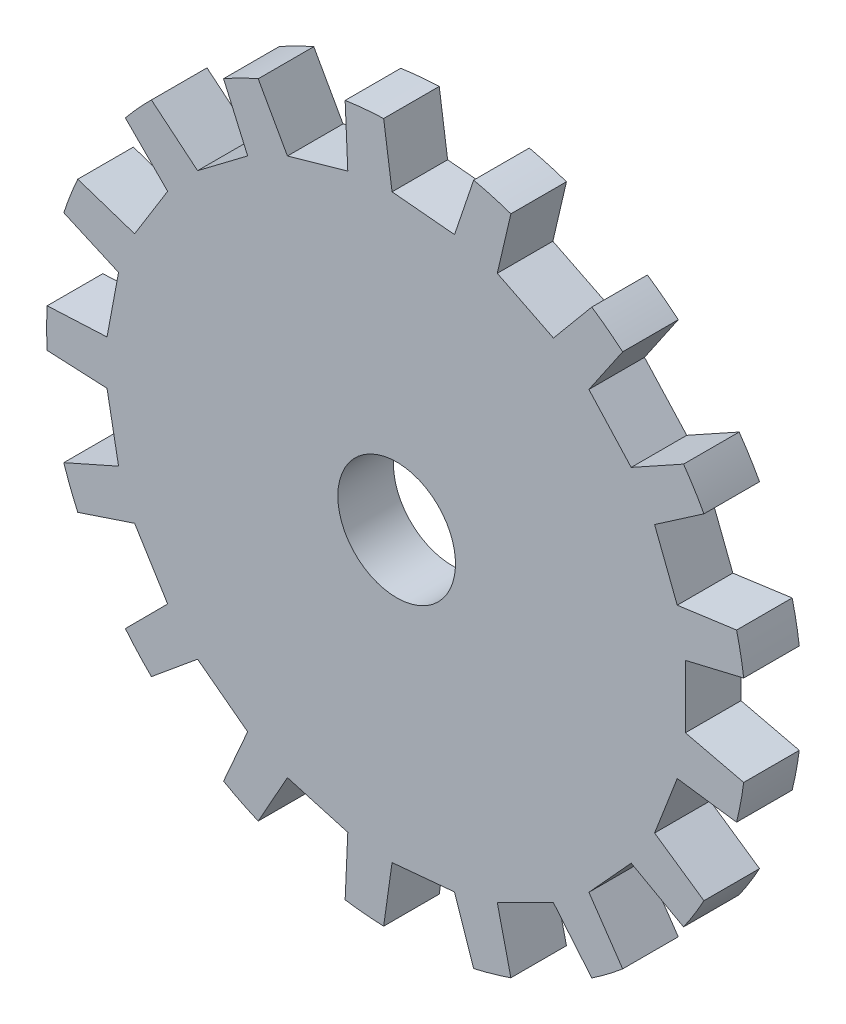
SolidWorks part; units mm, degrees
material "Plain Carbon Steel"
ref_plane "Front Plane" through (0, 0, 0) normal (0, 0, 1) x (1, 0, 0)
ref_plane "Top Plane" through (0, 0, 0) normal (0, 1, 0) x (1, 0, 0)
ref_plane "Right Plane" through (0, 0, 0) normal (1, 0, 0) x (0, 0, -1)
sketch "Sketch1" plane through (0, 0, 0) normal (0, 0, 1) x (1, 0, 0)
  circle A0 centre (0, 0) radius 28.3346
  dimension "D1" = 56.6692
extrude "Boss-Extrude1" add sketch "Sketch1" along normal blind 4.5
sketch "Sketch2" plane through (0, 0, 0) normal (0, 0, 1) x (1, 0, 0)
  line L0 (23.3784, -2.54) -> (29.5346, -4)
  line L1 (29.5346, -4) -> (29.5346, 4)
  line L2 (29.5346, 4) -> (23.3784, 2.54)
  line L3 (23.3784, 2.54) -> (23.3784, -2.54)
extrude "Cut-Extrude2" cut sketch "Sketch2" against normal blind 5.5 and the other way blind 5.5
ref_axis "Axis1" through (0, 0, -0.225) along (0, 0, 1)
pattern_circular "CirPattern1" count 17 over 360 about axis through (0, 0, -0.225) along (0, 0, 1) of "Cut-Extrude2"
sketch "Sketch3" plane through (0, 0, 0) normal (0, 0, 1) x (1, 0, 0)
  circle A0 centre (0, 0) radius 4.7625
  dimension "D1" = 9.525
extrude "Cut-Extrude4" cut sketch "Sketch3" against normal blind 6.5 and the other way blind 6.5
